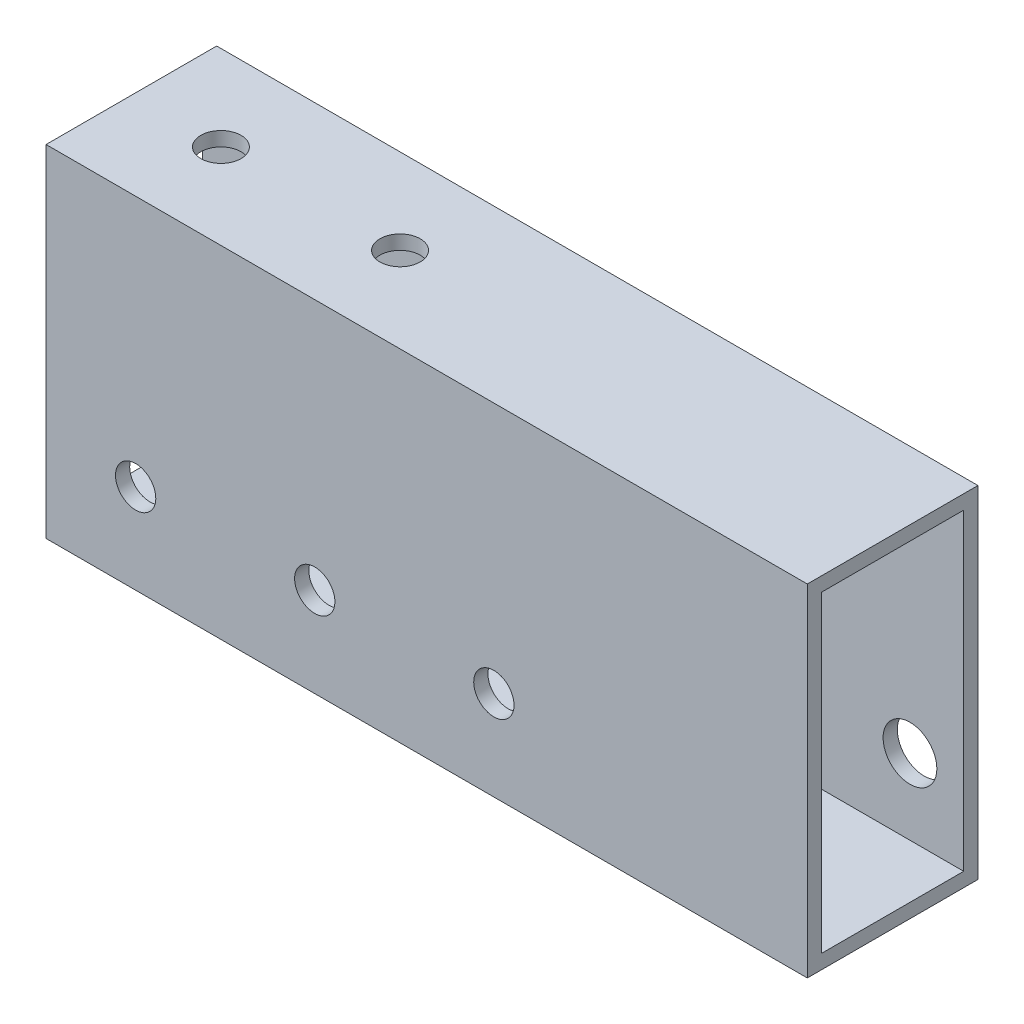
SolidWorks part; units mm, degrees
material "6061-T6 (SS)"
ref_plane "Front Plane" through (0, 0, 0) normal (0, 0, 1) x (1, 0, 0)
ref_plane "Top Plane" through (0, 0, 0) normal (0, 1, 0) x (1, 0, 0)
ref_plane "Right Plane" through (0, 0, 0) normal (1, 0, 0) x (0, 0, -1)
ref_plane "Plane1" through (100, 0, 0) normal (1, 0, 0) x (0, 0, -1)
sketch "Sketch1" plane through (0, 0, 0) normal (1, 0, 0) x (0, 0, -1)
  line L0 (19.05, -38.1) -> (0, -19.05) construction
  line L1 (-19.05, 38.1) -> (19.05, 38.1)
  line L2 (-19.05, 38.1) -> (-19.05, -38.1)
  line L3 (-19.05, -38.1) -> (19.05, -38.1)
  line L4 (19.05, 38.1) -> (19.05, -38.1)
  line L5 (-19.05, 38.1) -> (19.05, -38.1) construction
  line L6 (-19.05, -38.1) -> (19.05, 38.1) construction
  line L7 (0, 55) -> (0, -55) construction
  point P0 (0, 0)
  point P6 (0, -19.05)
  point P10 (0, 0)
  dimension "D1" = 38.1
  dimension "D2" = 76.2
  dimension "D3" = 45
extrude "Extrude-Thin1" add sketch "Sketch1" along normal offset from surface 30 and the other way blind 40 thin up to plane "Plane1" offset beyond the face yes thin type one direction reverse wall 3.175
hole_wizard "M8 Clearance Hole2" positions "Sketch2" profile "Sketch3" hole size "M8" standard "ANSI Metric" end condition through all
sketch "Sketch2" plane through (0, 0, -19.05) normal (0, 0, -1) x (-1, 0, 0)
  line L0 (-20, -18.1) -> (20, -18.1)
  line L1 (0, 55) -> (0, -55) construction
  line L2 (40, -38.1) -> (-130, -38.1) construction
  line L3 (-20, -18.1) -> (-60, -18.1)
  point P0 (20, -18.1)
  point P2 (-20, -18.1)
  point P9 (0, -18.1)
  point P20 (-60, -18.1)
  dimension "D1" = 40
  dimension "D2" = 20
sketch "Sketch3" plane through (-20, -18.1, -19.05) normal (1, 0, 0) x (0, 1, 0)
  line L0 (0, 0) -> (0, 38.1)
  line L1 (0, 38.1) -> (4.5, 38.1)
  line L2 (4.5, 38.1) -> (4.5, 0)
  line L5 (4.5, 0) -> (0, 0)
  line L11 (0, -6.35) -> (0, 107.95) construction
  dimension "Thru Hole Dia." = 9
  dimension "Thru Hole Depth" = 38.1
hole_wizard "M8 Clearance Hole3" positions "Sketch9" profile "Sketch10" hole size "M8" standard "ANSI Metric" end condition through all
sketch "Sketch9" plane through (0, -38.1, 0) normal (0, -1, 0) x (-1, 0, 0)
  line L0 (-20, 0) -> (20, 0)
  line L2 (-20, 19.05) -> (20, 19.05) construction
  point P1 (-20, 0)
  point P2 (20, 0)
sketch "Sketch10" plane through (20, -38.1, 0) normal (1, 0, 0) x (0, 0, -1)
  line L0 (0, 0) -> (0, 76.2)
  line L1 (0, 76.2) -> (4.5, 76.2)
  line L2 (4.5, 76.2) -> (4.5, 0)
  line L5 (4.5, 0) -> (0, 0)
  line L11 (0, -6.35) -> (0, 107.95) construction
  dimension "Thru Hole Dia." = 9
  dimension "Thru Hole Depth" = 76.2
hole_wizard "Ø12.0 (12) Diameter Hole1" positions "Sketch6" profile "Sketch7" hole size "Ø12.0" standard "ANSI Metric" end condition up to next
sketch "Sketch6" plane through (0, 0, -19.05) normal (0, 0, -1) x (-1, 0, 0)
  line L0 (-82, -18.1) -> (-118, -18.1)
  line L6 (-20, -18.1) -> (20, -18.1) construction
  line L7 (-100, 20.955) -> (-100, -20.955) construction
  point P0 (-118, -18.1)
  point P2 (-82, -18.1)
  point P23 (-100, -18.1)
  dimension "D1" = 36
sketch "Sketch7" plane through (118, -18.1, -19.05) normal (1, 0, 0) x (0, 1, 0)
  line L0 (0, 0) -> (0, 3.175)
  line L1 (0, 3.175) -> (6, 3.175)
  line L2 (6, 3.175) -> (6, 0)
  line L5 (6, 0) -> (0, 0)
  line L11 (0, -6.35) -> (0, 107.95) construction
  dimension "Thru Hole Dia." = 12
  dimension "Thru Hole Depth" = 3.175
